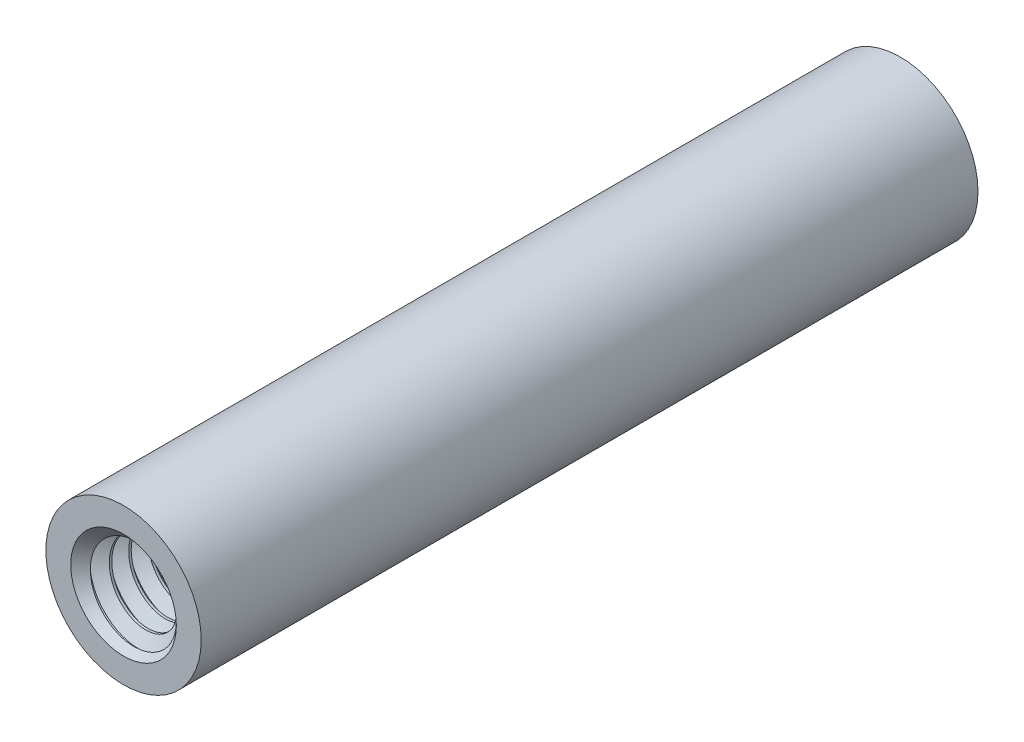
SolidWorks part; units mm, degrees
material "6061 Alloy"
ref_plane "Front Plane" through (0, 0, 0) normal (0, 0, 1) x (1, 0, 0)
ref_plane "Top Plane" through (0, 0, 0) normal (0, 1, 0) x (1, 0, 0)
ref_plane "Right Plane" through (0, 0, 0) normal (1, 0, 0) x (0, 0, -1)
sketch "Sketch3" plane through (0, 0, 0) normal (1, 0, 0) x (0, 0, -1)
  line L0 (-15.875, 0) -> (15.875, 0) construction
  line L1 (0, 3.175) -> (0, -3.175) construction
  line L2 (-15.875, 2.0828) -> (-15.875, -2.0828) construction
  point P2 (4.7625, 0)
  point P3 (-4.7625, 0)
  dimension "Length" = 31.75
  dimension "Min Thread Length" = 11.1125
  dimension "D1" = 11.1125
  dimension "Thread Dia" = 4.1656
  dimension "OD" = 6.35
ref_axis "Axis1" through (0, 3.175, 0) along (0, -1, 0)
sketch "Sketch10" plane through (0, 0, 0) normal (1, 0, 0) x (0, 0, -1)
  line L0 (15.875, 2.0828) -> (4.7625, 2.0828)
  line L1 (-15.875, 2.0828) -> (-4.7625, 2.0828)
  line L2 (4.7625, 2.0828) -> (4.7625, -2.0828)
  line L3 (-15.875, -2.0828) -> (-4.7625, -2.0828)
  line L4 (-4.7625, 2.0828) -> (-4.7625, -2.0828)
  line L5 (4.7625, -2.0828) -> (15.875, -2.0828)
sketch "Sketch13" plane through (0, 0, 0) normal (0, 0, 1) x (1, 0, 0)
  circle A0 centre (0, 0) radius 2.0828
extrude "Boss-Extrude1" add sketch "Sketch13" against normal up to vertex (-4.7625 mm away) from vertex at 15.875 starting at point (0, 0, 15.875)
sketch "Sketch14" plane through (0, 0, 15.875) normal (0, 0, 1) x (1, 0, 0)
  circle A1 centre (0, 0) radius 2.0828
  circle A2 centre (0, 0) radius 2.0828
  dimension "D1" = 0
curve "Helix/Spiral2" pitch 0.7937 height 11.9062 turns 15 parameters "Pitch"=0.7937
sketch "Sketch15" plane through (0, 0, 0) normal (1, 0, 0) x (0, 0, -1)
  line L0 (-16.5695, 2.0828) -> (-15.875, 2.0828)
  line L1 (-16.5695, 2.0828) -> (-16.2719, 1.5672)
  line L2 (-16.2719, 1.5672) -> (-16.1727, 1.5672)
  line L3 (-16.1727, 1.5672) -> (-15.875, 2.0828)
  line L4 (-16.2223, 1.5672) -> (-16.2223, 2.0828) construction
  line L5 (-16.4207, 1.825) -> (-16.0238, 1.825) construction
  dimension "D1" = 60
  dimension "D2" = 0.0992
  dimension "D3" = 0.3969
sweep "Cut-Sweep1" cut profiles "Sketch15" path "Helix/Spiral2" align with end faces yes
sketch "Sketch16" plane through (0, 0, 15.875) normal (0, 0, 1) x (1, 0, 0)
  circle A2 centre (0, 0) radius 2.159
  circle A3 centre (0, 0) radius 2.159
  dimension "D1" = 0.0762
extrude "Boss-Extrude2" add sketch "Sketch16" against normal through all draft 45
pattern_circular "CirPattern1" count 2 over 180 about axis through (0, 3.175, 0) along (0, -1, 0) of bodies 113
sketch "Sketch1" plane through (0, 0, 0) normal (0, 0, 1) x (1, 0, 0)
  circle A1 centre (0, 0) radius 2.0828 construction
  circle A2 centre (0, 0) radius 3.175
extrude "Extrude1" add sketch "Sketch1" along normal up to vertex (15.875 mm away) and the other way up to vertex (15.875 mm away) up to point (0, 0, 15.875) other way up to point (0, 0, -15.875)
combine bodies "Combine1" operation type subtract main body 101 bodies to subtract 114 113
equation "\"D1@Sketch3\" = \"Min Thread Length@Sketch3\""
equation "\"D3@Helix/Spiral2\" = \"Min Thread Length@Sketch3\"+\"Pitch@Helix/Spiral2\""
equation "\"D2@Sketch15\" = \"Pitch@Helix/Spiral2\"*.125"
equation "\"D3@Sketch15\" = \"Pitch@Helix/Spiral2\"*.5"
